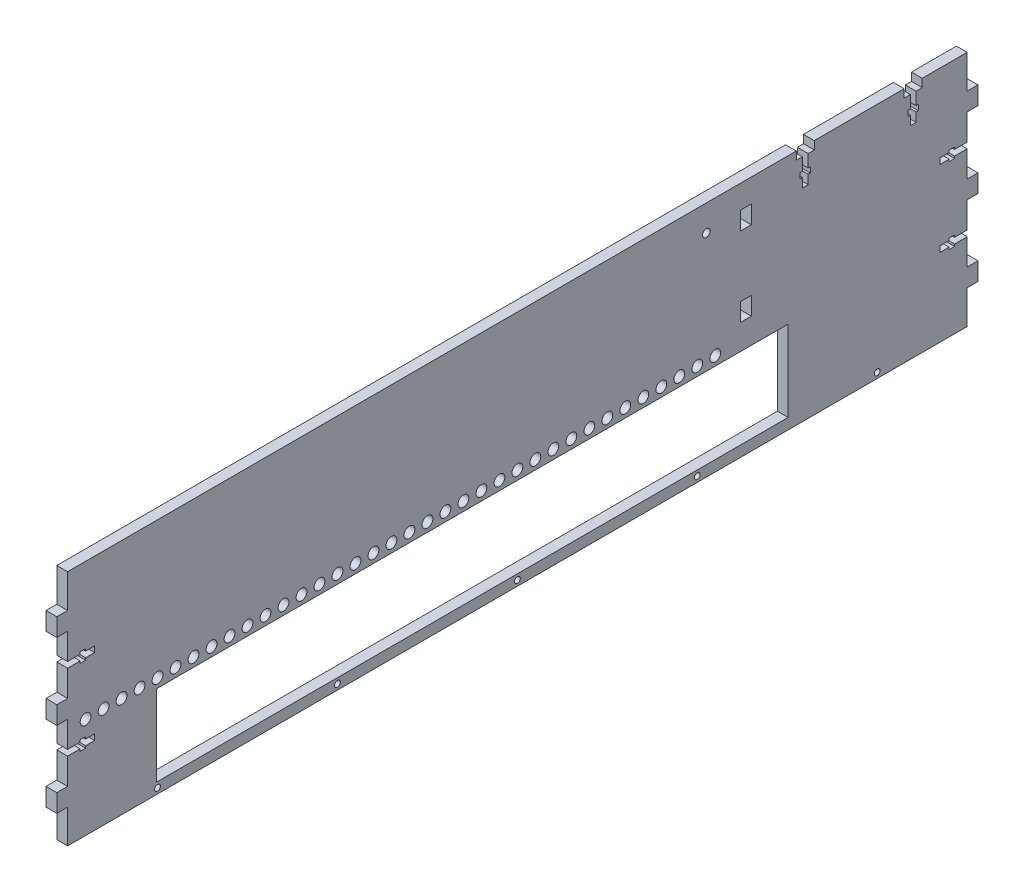
SolidWorks part; units mm, degrees
ref_plane "Front Plane" through (0, 0, 0) normal (0, 0, 1) x (1, 0, 0)
ref_plane "Top Plane" through (0, 0, 0) normal (0, 1, 0) x (1, 0, 0)
ref_plane "Right Plane" through (0, 0, 0) normal (1, 0, 0) x (0, 0, -1)
sketch "Sketch1" plane through (0, 0, 0) normal (1, 0, 0) x (0, 0, -1)
  line L1 (-250, -66) -> (250, -66)
  line L2 (-250, -66) -> (-250, 66)
  line L3 (-250, 66) -> (250, 66)
  line L4 (250, -66) -> (250, 66)
  line L5 (-250, -66) -> (250, 66) construction
  line L6 (-250, 66) -> (250, -66) construction
  point P0 (0, 0)
  dimension "D1" = 132
  dimension "D2" = 500
extrude "Boss-Extrude1" add sketch "Sketch1" along normal blind 6
sketch "Sketch4" plane through (0, 0, 250) normal (0, 0, 1) x (1, 0, 0)
  line L0 (0, 66) -> (0, -66) construction
  line L1 (0, 47.3321) -> (6, 47.3321)
  line L2 (0, 47.3321) -> (0, 37.3321)
  line L3 (0, 37.3321) -> (6, 37.3321)
  line L4 (6, 47.3321) -> (6, 37.3321)
  line L5 (6, 66) -> (6, -66) construction
  line L6 (0, 37.3321) -> (6, 37.3321) construction
  line L7 (0, -66) -> (0, 66) construction
  line L8 (6, 47.3321) -> (0, 47.3321) construction
  line L9 (0, -5) -> (6, -5) construction
  line L10 (0, -5) -> (6, -5)
  line L11 (0, -5) -> (0, 5)
  line L12 (0, 5) -> (6, 5)
  line L13 (6, -5) -> (6, 5)
  line L14 (6, -66) -> (6, 66) construction
  line L15 (6, 5) -> (0, 5) construction
  line L16 (6, -37.3321) -> (0, -37.3321) construction
  line L17 (0, -47.3321) -> (6, -47.3321)
  line L18 (0, -47.3321) -> (0, -37.3321)
  line L19 (0, -37.3321) -> (6, -37.3321)
  line L20 (6, -47.3321) -> (6, -37.3321)
  line L21 (0, -47.3321) -> (6, -47.3321) construction
extrude "Boss-Extrude2" add sketch "Sketch4" along normal blind 6
sketch "Sketch5" plane through (0, 0, 0) normal (-1, 0, 0) x (0, 0, 1)
  line L0 (250, 37.3321) -> (250, 5) construction
  line L1 (250, 5) -> (250, -5) construction
  line L2 (250, -5) -> (250, -37.3321) construction
  line L3 (250, 21.1661) -> (235, 21.1661) construction
  line L4 (240, -23.9661) -> (243, -18.3661) construction
  line L5 (250, 22.7661) -> (235, 22.7661)
  line L6 (240, -18.3661) -> (243, -23.9661) construction
  line L7 (250, 19.5661) -> (235, 19.5661)
  line L8 (250, -21.1661) -> (235, -21.1661) construction
  line L9 (250, 22.7661) -> (250, 19.5661)
  line L10 (235, 22.7661) -> (235, 19.5661)
  line L11 (243, -18.3661) -> (243, -23.9661)
  line L12 (240, -23.9661) -> (243, -23.9661)
  line L13 (250, 0) -> (222.8268, 0) construction
  line L14 (240, 18.3661) -> (243, 18.3661)
  line L15 (240, 18.3661) -> (240, 23.9661)
  line L16 (240, 23.9661) -> (243, 23.9661)
  line L17 (243, 18.3661) -> (243, 23.9661)
  line L18 (240, 18.3661) -> (243, 23.9661) construction
  line L19 (240, 23.9661) -> (243, 18.3661) construction
  line L20 (240, -18.3661) -> (240, -23.9661)
  line L21 (240, -18.3661) -> (243, -18.3661)
  line L22 (235, -22.7661) -> (235, -19.5661)
  line L23 (250, -22.7661) -> (250, -19.5661)
  line L24 (250, -19.5661) -> (235, -19.5661)
  line L25 (250, -22.7661) -> (235, -22.7661)
  point P20 (241.5, 21.1661)
  point P29 (241.5, -21.1661)
  dimension "D3" = 15
  dimension "D4" = 7
  dimension "D5" = 3
  dimension "D6" = 5.6
  dimension "D1" = 1.6
  dimension "D2" = 1.6
extrude "Cut-Extrude3" cut sketch "Sketch5" against normal up to next contours L17 L7 L9 L5 | L7 L17 L5 L15 | L5 L17 L16 L15 | L14 L17 L7 L15 | L7 L15 L5 L10 | L25 L23 L24 L11 | L25 L11 L24 L20 | L24 L11 L21 L20 | L11 L25 L20 L12 | L25 L20 L24 L22 region at (0, 21.1661, 246.5) region at (0, 21.1661, 241.5) region at (0, 23.3661, 241.5) region at (0, 21.1661, 237.5) region at (0, 18.9661, 241.5) region at (0, -18.9661, 241.5) region at (0, -21.1661, 246.5) region at (0, -21.1661, 241.5) region at (0, -23.3661, 241.5) region at (0, -21.1661, 237.5)
sketch "Sketch6" plane through (0, 0, -250) normal (0, 0, -1) x (-1, 0, 0)
  line L0 (0, 47.3321) -> (0, 37.3321) construction
  line L1 (0, 37.3321) -> (-6, 37.3321) construction
  line L2 (-6, 37.3321) -> (-6, 47.3321) construction
  line L3 (-6, 47.3321) -> (0, 47.3321) construction
  line L4 (0, 5) -> (0, -5) construction
  line L5 (0, -5) -> (-6, -5) construction
  line L6 (-6, -5) -> (-6, 5) construction
  line L7 (-6, 5) -> (0, 5) construction
  line L8 (0, -37.3321) -> (0, -47.3321) construction
  line L9 (0, -47.3321) -> (-6, -47.3321) construction
  line L10 (-6, -47.3321) -> (-6, -37.3321) construction
  line L11 (-6, -37.3321) -> (0, -37.3321) construction
  line L12 (0, 47.3321) -> (0, 37.3321)
  line L13 (0, 37.3321) -> (-6, 37.3321)
  line L14 (-6, 37.3321) -> (-6, 47.3321)
  line L15 (-6, 47.3321) -> (0, 47.3321)
  line L16 (0, 5) -> (0, -5)
  line L17 (0, -5) -> (-6, -5)
  line L18 (-6, -5) -> (-6, 5)
  line L19 (-6, 5) -> (0, 5)
  line L20 (0, -37.3321) -> (0, -47.3321)
  line L21 (0, -47.3321) -> (-6, -47.3321)
  line L22 (-6, -47.3321) -> (-6, -37.3321)
  line L23 (-6, -37.3321) -> (0, -37.3321)
extrude "Boss-Extrude3" add sketch "Sketch6" along normal blind 6
sketch "Sketch7" plane through (0, 0, 0) normal (-1, 0, 0) x (0, 0, 1)
  line L0 (0, 0) -> (0, -63.2146) construction
  line L1 (240, 22.7661) -> (240, 23.9661) construction
  line L2 (240, 22.7661) -> (235, 22.7661) construction
  line L3 (235, 22.7661) -> (235, 19.5661) construction
  line L4 (240, 19.5661) -> (235, 19.5661) construction
  line L5 (240, 18.3661) -> (240, 19.5661) construction
  line L6 (240, 18.3661) -> (243, 18.3661) construction
  line L7 (243, 18.3661) -> (243, 19.5661) construction
  line L8 (250, 19.5661) -> (243, 19.5661) construction
  line L9 (250, 22.7661) -> (243, 22.7661) construction
  line L10 (240, 23.9661) -> (243, 23.9661) construction
  line L11 (243, 22.7661) -> (243, 23.9661) construction
  line L12 (240, 22.7661) -> (235, 22.7661) construction
  line L13 (235, 22.7661) -> (235, 19.5661) construction
  line L14 (240, 19.5661) -> (235, 19.5661) construction
  line L15 (240, 18.3661) -> (240, 19.5661) construction
  line L16 (240, 18.3661) -> (243, 18.3661) construction
  line L17 (243, 18.3661) -> (243, 19.5661) construction
  line L18 (250, 19.5661) -> (243, 19.5661) construction
  line L19 (250, 22.7661) -> (243, 22.7661) construction
  line L20 (240, 23.9661) -> (243, 23.9661) construction
  line L21 (243, 22.7661) -> (243, 23.9661) construction
  line L22 (240, 22.7661) -> (240, 23.9661) construction
  line L23 (250, -19.5661) -> (243, -19.5661) construction
  line L24 (240, -18.3661) -> (243, -18.3661) construction
  line L25 (243, -18.3661) -> (243, -19.5661) construction
  line L26 (240, -18.3661) -> (240, -19.5661) construction
  line L27 (240, -19.5661) -> (235, -19.5661) construction
  line L28 (235, -22.7661) -> (235, -19.5661) construction
  line L29 (240, -22.7661) -> (235, -22.7661) construction
  line L30 (240, -22.7661) -> (240, -23.9661) construction
  line L31 (240, -23.9661) -> (243, -23.9661) construction
  line L32 (243, -22.7661) -> (243, -23.9661) construction
  line L33 (250, -22.7661) -> (243, -22.7661) construction
  line L34 (250, -19.5661) -> (243, -19.5661) construction
  line L35 (240, -18.3661) -> (243, -18.3661) construction
  line L36 (243, -18.3661) -> (243, -19.5661) construction
  line L37 (240, -18.3661) -> (240, -19.5661) construction
  line L38 (240, -19.5661) -> (235, -19.5661) construction
  line L39 (235, -22.7661) -> (235, -19.5661) construction
  line L40 (240, -22.7661) -> (235, -22.7661) construction
  line L41 (240, -22.7661) -> (240, -23.9661) construction
  line L42 (240, -23.9661) -> (243, -23.9661) construction
  line L43 (243, -22.7661) -> (243, -23.9661) construction
  line L44 (250, -22.7661) -> (243, -22.7661) construction
  line L45 (250, 22.7661) -> (250, 19.5661) construction
  line L46 (250, -19.5661) -> (250, -22.7661) construction
  line L47 (-250, -19.5661) -> (-250, -22.7661)
  line L48 (-250, 22.7661) -> (-250, 19.5661)
  line L49 (-250, -22.7661) -> (-243, -22.7661)
  line L50 (-243, -22.7661) -> (-243, -23.9661)
  line L51 (-240, -23.9661) -> (-243, -23.9661)
  line L52 (-240, -22.7661) -> (-240, -23.9661)
  line L53 (-240, -22.7661) -> (-235, -22.7661)
  line L54 (-235, -22.7661) -> (-235, -19.5661)
  line L55 (-240, -19.5661) -> (-235, -19.5661)
  line L56 (-240, -18.3661) -> (-240, -19.5661)
  line L57 (-243, -18.3661) -> (-243, -19.5661)
  line L58 (-240, -18.3661) -> (-243, -18.3661)
  line L59 (-250, -19.5661) -> (-243, -19.5661)
  line L60 (-240, 22.7661) -> (-240, 23.9661)
  line L61 (-243, 22.7661) -> (-243, 23.9661)
  line L62 (-240, 23.9661) -> (-243, 23.9661)
  line L63 (-250, 22.7661) -> (-243, 22.7661)
  line L64 (-250, 19.5661) -> (-243, 19.5661)
  line L65 (-243, 18.3661) -> (-243, 19.5661)
  line L66 (-240, 18.3661) -> (-243, 18.3661)
  line L67 (-240, 18.3661) -> (-240, 19.5661)
  line L68 (-240, 19.5661) -> (-235, 19.5661)
  line L69 (-235, 22.7661) -> (-235, 19.5661)
  line L70 (-240, 22.7661) -> (-235, 22.7661)
extrude "Cut-Extrude4" cut sketch "Sketch7" against normal up to next
sketch "Sketch8" plane through (0, 0, 0) normal (-1, 0, 0) x (0, 0, 1)
  line L0 (200, -15.55) -> (-150, -15.55) construction
  line L1 (200, -15.55) -> (-150, -15.55) construction
  line L2 (200, -15.55) -> (200, -60) construction
  line L3 (200, -15.55) -> (200, -60) construction
  line L186 (-150, -15.55) -> (-150, -60) construction
  line L187 (-150, -60) -> (200, -60) construction
  line L188 (200.5, -15.05) -> (200.5, -60)
  line L189 (200.5, -15.05) -> (-150.5, -15.05)
  line L190 (-150.5, -15.05) -> (-150.5, -60)
  line L191 (-150.5, -60) -> (200.5, -60)
  dimension "D1" = 0.5
extrude "Cut-Extrude5" cut sketch "Sketch8" against normal up to next
sketch "Sketch10" plane through (6, 0, 0) normal (1, 0, 0) x (0, 0, -1)
  line L0 (0, 0) -> (0, -66) construction
  line L1 (-250, -66) -> (250, -66) construction
  line L2 (0, -63) -> (250, -63) construction
  line L3 (250, -66) -> (250, -47.3321) construction
  circle A0 centre (0, -63) radius 1.6
  circle A1 centre (100, -63) radius 1.6
  circle A2 centre (200, -63) radius 1.6
  circle A3 centre (-100, -63) radius 1.6
  circle A4 centre (-200, -63) radius 1.6
  dimension "D2" = 3.2
  dimension "D1" = 3
  dimension "D3" = 100
  dimension "D4" = 100
extrude "Cut-Extrude7" cut sketch "Sketch10" against normal up to next
sketch "Sketch11" plane through (6, 0, 0) normal (1, 0, 0) x (0, 0, -1)
  line L0 (130, 43) -> (130, 53) construction
  line L1 (130, 53) -> (124, 53) construction
  line L2 (124, 53) -> (124, 43) construction
  line L3 (124, 43) -> (130, 43) construction
  line L4 (130, -1) -> (130, 9) construction
  line L5 (130, 9) -> (124, 9) construction
  line L6 (124, 9) -> (124, -1) construction
  line L7 (124, -1) -> (130, -1) construction
  line L8 (130, 43) -> (130, 53)
  line L9 (130, 53) -> (124, 53)
  line L10 (124, 53) -> (124, 43)
  line L11 (124, 43) -> (130, 43)
  line L12 (130, -1) -> (130, 9)
  line L13 (130, 9) -> (124, 9)
  line L14 (124, 9) -> (124, -1)
  line L15 (124, -1) -> (130, -1)
extrude "Cut-Extrude8" cut sketch "Sketch11" against normal up to next
sketch "Sketch12" plane through (0, 0, 0) normal (-1, 0, 0) x (0, 0, 1)
  line L0 (-124, 53) -> (-124, 43) construction
  line L1 (-250, 66) -> (250, 66) construction
  circle A0 centre (-105, 51.5) radius 2.1
  dimension "D1" = 19
  dimension "D3" = 4.2
  dimension "D2" = 14.5
extrude "Cut-Extrude9" cut sketch "Sketch12" against normal up to next
sketch "Sketch13" plane through (0, 66, 0) normal (0, 1, 0) x (1, 0, 0)
  line L0 (6, 250) -> (6, -250) construction
  line L1 (0, 215) -> (6, 215)
  line L2 (0, 215) -> (0, 225)
  line L3 (0, 225) -> (6, 225)
  line L4 (6, 215) -> (6, 225)
  line L5 (0, 215) -> (6, 225) construction
  line L6 (0, 225) -> (6, 215) construction
  line L7 (6, 225) -> (0, 225) construction
  line L8 (6, 165) -> (0, 165) construction
  line L9 (0, 155) -> (6, 155)
  line L10 (0, 155) -> (0, 165)
  line L11 (0, 165) -> (6, 165)
  line L12 (6, 155) -> (6, 165)
  line L13 (0, 155) -> (6, 165) construction
  line L14 (0, 165) -> (6, 155) construction
  point P0 (3, 220)
  point P10 (3, 160)
extrude "Cut-Extrude10" cut sketch "Sketch13" against normal blind 4.5
sketch "Sketch14" plane through (0, 0, 0) normal (-1, 0, 0) x (0, 0, 1)
  circle A0 centre (240, -10) radius 3 construction
  circle A1 centre (240, -10) radius 3
  circle A2 centre (230, -10) radius 3
  circle A3 centre (220, -10) radius 3
  circle A4 centre (210, -10) radius 3
  circle A5 centre (200, -10) radius 3
  circle A6 centre (190, -10) radius 3
  circle A7 centre (180, -10) radius 3
  circle A8 centre (170, -10) radius 3
  circle A9 centre (160, -10) radius 3
  circle A10 centre (150, -10) radius 3
  circle A11 centre (140, -10) radius 3
  circle A12 centre (130, -10) radius 3
  circle A13 centre (120, -10) radius 3
  circle A14 centre (110, -10) radius 3
  circle A15 centre (100, -10) radius 3
  circle A16 centre (90, -10) radius 3
  circle A17 centre (80, -10) radius 3
  circle A18 centre (70, -10) radius 3
  circle A19 centre (60, -10) radius 3
  circle A20 centre (50, -10) radius 3
  circle A21 centre (40, -10) radius 3
  circle A22 centre (30, -10) radius 3
  circle A23 centre (20, -10) radius 3
  circle A24 centre (10, -10) radius 3
  circle A25 centre (0, -10) radius 3
  circle A26 centre (-10, -10) radius 3
  circle A27 centre (-20, -10) radius 3
  circle A28 centre (-30, -10) radius 3
  circle A29 centre (-40, -10) radius 3
  circle A30 centre (-50, -10) radius 3
  circle A31 centre (-60, -10) radius 3
  circle A32 centre (-70, -10) radius 3
  circle A33 centre (-80, -10) radius 3
  circle A34 centre (-90, -10) radius 3
  circle A35 centre (-100, -10) radius 3
  circle A36 centre (-110, -10) radius 3
  dimension "D1" = 36
extrude "Cut-Extrude11" cut sketch "Sketch14" against normal up to next (6 mm away)
sketch "Sketch15" plane through (6, 0, 0) normal (1, 0, 0) x (0, 0, -1)
  line L0 (160, 61.5) -> (160, 46.5) construction
  line L1 (155, 61.5) -> (165, 61.5) construction
  line L2 (220, 61.5) -> (220, 46.5) construction
  line L3 (215, 61.5) -> (225, 61.5) construction
  line L4 (160, 46.5) -> (220, 46.5) construction
  line L5 (190, 46.5) -> (190, 66) construction
  line L6 (215, 66) -> (165, 66) construction
  line L7 (158.4, 61.5) -> (158.4, 54.5)
  line L8 (161.6, 61.5) -> (161.6, 54.5)
  line L9 (158.4, 61.5) -> (161.6, 61.5)
  line L10 (158.4, 46.5) -> (161.6, 46.5)
  line L11 (161.6, 51.5) -> (162.8, 51.5)
  line L12 (157.2, 54.5) -> (158.4, 54.5)
  line L13 (157.2, 54.5) -> (157.2, 51.5)
  line L14 (157.2, 51.5) -> (158.4, 51.5)
  line L15 (162.8, 54.5) -> (162.8, 51.5)
  line L16 (157.2, 54.5) -> (162.8, 51.5) construction
  line L17 (157.2, 51.5) -> (162.8, 54.5) construction
  line L18 (161.6, 54.5) -> (162.8, 54.5)
  line L19 (158.4, 51.5) -> (158.4, 46.5)
  line L20 (158.4, 61.5) -> (158.4, 46.5) construction
  line L21 (161.6, 51.5) -> (161.6, 46.5)
  line L22 (161.6, 61.5) -> (161.6, 46.5) construction
  line L23 (222.8, 51.5) -> (217.2, 54.5) construction
  line L24 (222.8, 54.5) -> (217.2, 51.5) construction
  line L25 (220, 61.5) -> (220, 46.5) construction
  line L26 (218.4, 51.5) -> (218.4, 46.5)
  line L27 (221.6, 51.5) -> (221.6, 46.5)
  line L28 (218.4, 54.5) -> (217.2, 54.5)
  line L29 (217.2, 54.5) -> (217.2, 51.5)
  line L30 (222.8, 51.5) -> (221.6, 51.5)
  line L31 (222.8, 54.5) -> (222.8, 51.5)
  line L32 (222.8, 54.5) -> (221.6, 54.5)
  line L33 (218.4, 51.5) -> (217.2, 51.5)
  line L34 (221.6, 46.5) -> (218.4, 46.5)
  line L35 (221.6, 61.5) -> (218.4, 61.5)
  line L36 (218.4, 61.5) -> (218.4, 54.5)
  line L37 (221.6, 61.5) -> (221.6, 54.5)
  point P16 (160, 53)
  point P37 (220, 53)
  dimension "D3" = 15
  dimension "D4" = 7
  dimension "D5" = 3
  dimension "D6" = 5.6
  dimension "D1" = 1.6
  dimension "D2" = 1.6
extrude "Cut-Extrude12" cut sketch "Sketch15" against normal up to next
